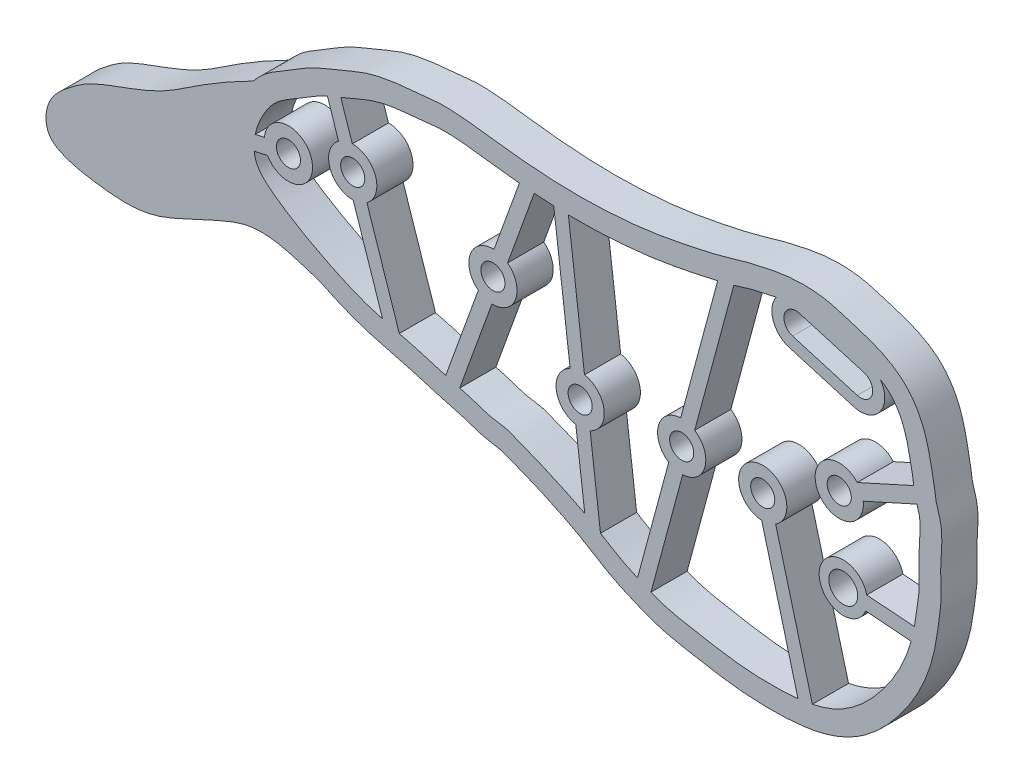
SolidWorks part; units mm, degrees
ref_plane "Спереди" through (0, 0, 0) normal (0, 0, 1) x (1, 0, 0)
ref_plane "Сверху" through (0, 0, 0) normal (0, 1, 0) x (1, 0, 0)
ref_plane "Справа" through (0, 0, 0) normal (1, 0, 0) x (0, 0, -1)
other "Configuration Table"
sketch "Sketch1" plane through (0, 0, 0) normal (0, 0, 1) x (1, 0, 0)
  line L0 (-54.4942, -36.8161) -> (-49.7734, -50.9593) construction
  line L5 (-50.4662, -50.7786) -> (-52.9099, -43.4575)
  line L6 (-54.1176, -39.8395) -> (-55.0485, -37.0505)
  line L8 (-52.9793, -39.4595) -> (-53.9346, -36.5976)
  line L9 (-51.7717, -43.0776) -> (-49.0827, -51.1337)
  line L10 (-44.6539, -52.3842) -> (-38.5095, -35.4122) construction
  line L11 (-6.4818, -51.4155) -> (-12.265, -50.9822) construction
  line L12 (-41.2312, -41.1674) -> (-39.127, -35.3552)
  line L14 (-37.8898, -35.4629) -> (-40.1029, -41.5759)
  line L15 (-42.5296, -44.7539) -> (-45.2324, -52.2194)
  line L16 (-41.4013, -45.1624) -> (-44.0733, -52.5428)
  line L17 (-33.0514, -56.7428) -> (-35.6666, -35.5833) construction
  line L18 (-36.274, -35.5605) -> (-34.9137, -46.5669)
  line L19 (-35.0602, -35.5983) -> (-33.7227, -46.4197)
  line L20 (-28.7671, -59.0348) -> (-22.0114, -33.9745) construction
  line L21 (-22.6779, -34.1417) -> (-25.7467, -45.5255)
  line L22 (-21.3407, -33.7919) -> (-24.5881, -45.8379)
  line L23 (-15.4183, -60.7418) -> (-18.9436, -47.5231) construction
  line L24 (-16.018, -60.8216) -> (-19.0319, -49.5205)
  line L25 (-14.8259, -60.6345) -> (-17.8724, -49.2112)
  line L26 (-6.3189, -41.3366) -> (-12.597, -44.1796) construction
  line L27 (-6.4229, -40.7251) -> (-11.1072, -42.8463)
  line L28 (-6.1531, -41.9202) -> (-10.6122, -43.9394)
  line L29 (-16.1872, -34.0479) -> (-10.8235, -35.627) construction
  line L34 (-34.1152, -53.0271) -> (-34.4458, -50.3524) construction
  line L35 (-34.4458, -50.3524) -> (-33.7016, -56.3739)
  line L37 (-33.2549, -50.2052) -> (-32.3983, -57.1358)
  line L43 (-26.7395, -49.2084) -> (-29.3266, -58.8049)
  line L45 (-25.5809, -49.5207) -> (-28.2081, -59.266)
  line L52 (-15.9048, -33.0886) -> (-10.541, -34.6677)
  line L55 (-42.5296, -44.7539) -> (-45.2324, -52.2194) construction
  line L56 (-6.36, -50.823) -> (-10.3184, -50.5264)
  line L57 (-6.36, -50.823) -> (-10.3184, -50.5264)
  line L58 (-16.4697, -35.0072) -> (-11.1059, -36.5863)
  line L59 (-16.1872, -34.0479) -> (-10.8235, -35.627) construction
  line L60 (-15.6224, -32.1293) -> (-10.2586, -33.7084)
  line L61 (-16.7521, -35.9665) -> (-11.3883, -37.5456)
  line L62 (-6.6306, -52.0061) -> (-10.408, -51.723)
  line L63 (-61.1201, -43.4425) -> (-58.2756, -42.8039) construction
  line L64 (-60.2679, -42.6363) -> (-61.0321, -42.8078)
  line L65 (-60.005, -43.8071) -> (-61.1153, -44.0564)
  arc A2 (-51.7717, -43.0776) -> (-52.9793, -39.4595) centre (-52.9446, -41.4585) ccw
  circle A3 centre (-52.9446, -41.4585) radius 1
  arc A4 (-41.4013, -45.1624) -> (-40.1029, -41.5759) centre (-41.3162, -43.1649) ccw
  circle A5 centre (-41.3162, -43.1649) radius 1
  arc A6 (-33.2549, -50.2052) -> (-33.7227, -46.4197) centre (-34.0843, -48.386) ccw
  circle A7 centre (-34.0843, -48.386) radius 1
  arc A8 (-25.5809, -49.5207) -> (-24.5881, -45.8379) centre (-25.6638, -47.5231) ccw
  circle A9 centre (-25.6638, -47.5231) radius 1
  circle A11 centre (-18.9436, -47.5231) radius 1
  arc A14 (-11.1072, -42.8463) -> (-10.6122, -43.9394) centre (-12.597, -44.1796) ccw
  circle A15 centre (-12.597, -44.1796) radius 1
  arc A20 (-17.8724, -49.2112) -> (-19.0319, -49.5205) centre (-18.9436, -47.5231) ccw
  arc A26 (-10.3184, -50.5264) -> (-10.408, -51.723) centre (-12.265, -50.9822) ccw
  circle A29 centre (-12.265, -50.9822) radius 1.2
  arc A30 (-15.9048, -33.0886) -> (-16.4697, -35.0072) centre (-16.1872, -34.0479) ccw
  arc A31 (-11.1059, -36.5863) -> (-10.541, -34.6677) centre (-10.8235, -35.627) ccw
  arc A32 (-54.1176, -39.8395) -> (-52.9099, -43.4575) centre (-52.9446, -41.4585) ccw
  arc A33 (-15.6224, -32.1293) -> (-16.7521, -35.9665) centre (-16.1872, -34.0479) ccw
  arc A34 (-11.3883, -37.5456) -> (-10.2586, -33.7084) centre (-10.8235, -35.627) ccw
  arc A37 (-41.2312, -41.1674) -> (-42.5296, -44.7539) centre (-41.3162, -43.1649) ccw
  arc A42 (-34.9137, -46.5669) -> (-34.4458, -50.3524) centre (-34.0843, -48.386) ccw
  arc A47 (-25.7467, -45.5255) -> (-26.7395, -49.2084) centre (-25.6638, -47.5231) ccw
  arc A49 (-56.5864, -44.0651) -> (-56.5834, -44.0611) centre (-58.2756, -42.8039) ccw
  arc A50 (-60.005, -43.8071) -> (-60.2679, -42.6363) centre (-58.2756, -42.8039) ccw
  circle A51 centre (-58.2756, -42.8039) radius 1
  spline S1 degree 3 poles (-58.7581, -48.9922) (-59.7104, -48.3888) (-60.601, -47.7689) (-61.439, -47.0975) (-62.1184, -46.3263) (-62.5768, -45.5944) (-62.8752, -44.6749) (-62.9472, -43.8512) (-62.9111, -43.1163) (-62.7679, -42.2009) (-62.4279, -41.1226) (-61.9297, -40.1381) (-61.4448, -39.3703) (-60.8782, -38.6441) (-60.0099, -37.8528) (-59.0035, -37.2461) (-58.1744, -36.7728) (-57.3271, -36.2387) (-56.3554, -35.6614) (-55.2169, -35.1525) (-54.2864, -34.812) (-53.4311, -34.4398) (-52.4291, -34.0078) (-51.2557, -33.61) (-50.0717, -33.3845) (-49.0452, -33.2306) (-47.8281, -33.1472) (-47.1214, -33.0685) (-45.8394, -32.9) (-44.6534, -32.9307) (-43.5686, -33.0146) (-42.1571, -33.1777) (-40.5095, -33.4038) (-38.5454, -33.6125) (-35.9409, -33.8049) (-33.3406, -33.8329) (-30.7567, -33.6781) (-28.7942, -33.4888) (-26.9201, -33.1962) (-24.9503, -32.8067) (-23.3497, -32.461) (-22.2655, -32.183) (-21.6495, -32.0089) (-21.2094, -31.8775) (-20.7095, -31.7135) (-19.878, -31.4995) (-19.1412, -31.3406) (-18.0288, -31.0843) (-16.5225, -30.8594) (-14.9286, -30.8163) (-13.4817, -31.0389) (-12.6301, -31.275) (-12.133, -31.4395) (-11.6411, -31.5873) (-10.8921, -31.8106) (-9.8671, -32.1394) (-8.5679, -32.7011) (-7.2519, -33.5877) (-6.2079, -34.8676) (-5.5594, -36.216) (-5.2408, -37.3079) (-5.0596, -38.1183) (-4.9425, -38.7029) (-4.8586, -39.1344) (-4.7764, -39.5181) (-4.6916, -40.024) (-4.6394, -40.5082) (-4.5811, -40.8969) (-4.4823, -41.2423) (-4.2813, -41.8514) (-4.1203, -42.6037) (-4.0747, -43.397) (-4.1171, -44.3126) (-4.1787, -45.2836) (-4.1993, -45.9221) (-4.1608, -46.9219) (-4.1506, -47.8891) (-4.2242, -48.6749) (-4.293, -49.0981) (-4.341, -49.3937) (-4.4, -49.8627) (-4.483, -50.5252) (-4.5958, -51.2074) (-4.7781, -52.079) (-5.1851, -53.5482) (-6.0146, -55.4786) (-7.3401, -57.5438) (-8.9971, -59.5041) (-11.088, -61.2325) (-13.7073, -62.3368) (-16.2947, -62.7054) (-18.6823, -62.767) (-21.1287, -62.6183) (-23.0787, -62.3194) (-24.5778, -62.0499) (-25.6889, -61.8523) (-26.8868, -61.6099) (-27.9556, -61.3023) (-28.7638, -60.9861) (-29.2891, -60.7653) (-29.7912, -60.5614) (-30.3561, -60.3273) (-30.9518, -60.0497) (-31.6951, -59.6598) (-32.5624, -59.1498) (-33.5293, -58.5502) (-34.7253, -57.8417) (-36.2969, -57.0762) (-38.0088, -56.3126) (-39.3047, -55.814) (-40.3059, -55.3901) (-40.6535, -55.2776) (-41.0437, -55.2098) (-41.6818, -55.1266) (-42.474, -54.929) (-43.0705, -54.7168) (-43.5262, -54.5599) (-43.9971, -54.425) (-44.7148, -54.2363) (-45.6675, -53.9705) (-47.1182, -53.541) (-48.8494, -53.0287) (-51.0345, -52.5269) (-53.2229, -51.8118) (-54.8479, -51.08) (-56.3053, -50.3685) (-57.5646, -49.6942) (-58.7581, -48.9922) (-59.7104, -48.3888) (-60.601, -47.7689) knots -0.027589 -0.015625 -0.007812 0 0.007812 0.015625 0.019531 0.023437 0.027344 0.03125 0.035156 0.039062 0.046875 0.054687 0.059556 0.063462 0.070312 0.078125 0.085937 0.09375 0.101562 0.109375 0.117187 0.125 0.132812 0.140625 0.148437 0.15625 0.164062 0.171875 0.179687 0.1875 0.195312 0.203125 0.21875 0.234375 0.25 0.28125 0.296875 0.3125 0.328125 0.34375 0.359375 0.367187 0.371094 0.375 0.378906 0.382812 0.390625 0.398437 0.40625 0.421875 0.429687 0.433594 0.4375 0.441406 0.445312 0.453125 0.460937 0.46875 0.476562 0.484375 0.492187 0.496094 0.5 0.503906 0.505859 0.507812 0.511719 0.515625 0.519531 0.523437 0.527344 0.53125 0.535156 0.539062 0.546875 0.554687 0.5625 0.566406 0.568359 0.570312 0.574219 0.578125 0.582031 0.585937 0.59375 0.609375 0.625 0.640625 0.65625 0.671875 0.6875 0.703125 0.71875 0.734375 0.742187 0.75 0.757812 0.765625 0.769531 0.773437 0.777344 0.78125 0.785156 0.789062 0.796875 0.804687 0.8125 0.828125 0.84375 0.851562 0.859375 0.863281 0.867187 0.871094 0.875 0.878906 0.882812 0.886719 0.890625 0.898437 0.90625 0.921875 0.9375 0.953125 0.964598 0.972411 0.984375 0.992187 1 1.007812 1.015625 1.019531 only from (-59.7001, -48.386) to (-59.7001, -48.386)
  spline S2 degree 3 poles (-54.8378, -49.1612) (-57.6604, -47.6241) (-59.8772, -46.0799) (-61.1016, -44.9748) (-61.19, -42.8792) (-60.5369, -41.1939) (-59.2773, -39.4251) (-57.3309, -38.4175) (-55.4721, -37.1478) (-53.2151, -36.3584) (-51.2833, -35.3978) (-49.5351, -35.1222) (-48.3072, -34.966) (-47.2995, -34.9312) (-45.9793, -34.697) (-43.9653, -34.742) (-40.8542, -35.194) (-36.962, -35.5881) (-33.9262, -35.6271) (-31.9892, -35.554) (-30.8887, -35.4887) (-29.5808, -35.3714) (-27.6433, -35.1578) (-24.6742, -34.6016) (-21.912, -33.9992) (-19.9812, -33.3713) (-19.0765, -33.1767) (-17.7192, -32.8438) (-15.8054, -32.5785) (-14.0131, -32.7113) (-11.5739, -33.5264) (-8.8287, -34.1518) (-7.065, -36.9423) (-6.7879, -38.7114) (-6.4527, -40.2945) (-6.4104, -41.2062) (-5.9587, -42.4484) (-5.8567, -43.2131) (-5.9542, -44.844) (-6.0378, -46.2993) (-5.8798, -47.7388) (-6.1409, -49.2063) (-6.4685, -52.3712) (-8.2087, -56.1917) (-12.2182, -60.2134) (-15.6942, -60.8453) (-17.4574, -60.9255) (-18.4504, -60.9397) (-19.983, -60.9127) (-22.1617, -60.661) (-24.8025, -60.1784) (-26.9948, -59.7888) (-28.675, -59.0656) (-30.7159, -58.261) (-33.245, -56.49) (-36.0164, -55.2271) (-37.9357, -54.4025) (-39.0582, -53.9787) (-40.2188, -53.4584) (-41.5664, -53.3759) (-42.8626, -52.8536) (-45.1527, -52.2761) (-48.0976, -51.3224) (-51.3756, -50.6084) (-54.8378, -49.1612) (-57.6604, -47.6241) (-59.8772, -46.0799) knots -0.078621 -0.053539 -0.039111 0 0.008418 0.024992 0.034759 0.054839 0.065896 0.084166 0.104395 0.11788 0.139207 0.153886 0.158466 0.167836 0.177148 0.189373 0.214163 0.249835 0.279723 0.284249 0.294647 0.305206 0.314606 0.339694 0.375025 0.37997 0.386562 0.396484 0.411656 0.431742 0.437535 0.469592 0.482501 0.504001 0.506417 0.516135 0.523104 0.532522 0.536639 0.545133 0.566484 0.569737 0.578233 0.624864 0.662471 0.68872 0.696194 0.699273 0.709375 0.72807 0.744781 0.765339 0.774026 0.78277 0.810922 0.837688 0.846033 0.85436 0.862697 0.872259 0.882004 0.891572 0.921379 0.946461 0.960889 1 1.008418 1.024992 1.034759 only from (-58.7055, -46.8858) to (-58.7055, -46.8858)
  spline S3 degree 3 poles (-61.1941, -39.0539) (-62.626, -39.7821) (-65.2082, -41.2079) (-68.8393, -43.8366) (-72.316, -44.9962) (-74.9893, -46.0569) (-76.7811, -47.3826) (-78.4745, -48.9002) (-78.4678, -51.4704) (-76.4876, -52.5204) (-73.8899, -52.9864) (-69.8015, -53.368) (-66.6063, -51.6264) (-63.7164, -50.3565) (-60.4815, -48.928) (-57.3243, -50.15) (-55.5648, -50.7285) knots 0 0 0 0 0.105046 0.193261 0.291014 0.343614 0.380043 0.43698 0.487582 0.515276 0.574689 0.662804 0.775463 0.804075 0.870738 1 1 1 1
  point P15 (-13.5054, -34.8374)
  point P22 (-13.5054, -34.8374)
  point P47 (-54.612, -36.8211)
  point P49 (-49.7734, -50.9822)
  point P51 (0, 0)
  point P55 (-42.4093, -52.975)
  point P61 (-19.7924, -49.2084)
  point P71 (0, 0)
  point P75 (-33.8709, -44.3599)
  point P87 (-44.6503, -52.3852)
  point P91 (-38.5095, -35.3552)
  point P106 (-34.1152, -48.386)
  point P113 (-19.0319, -47.5231)
  dimension "D19" = 2
  dimension "D6" = 0.6
  dimension "D10" = 0.6
  dimension "D14" = 0.6
  dimension "D15" = 0.6
  dimension "D11" = 0.6
  dimension "D12" = 0.6
  dimension "D4" = 0.6
  dimension "D5" = 0.6
  dimension "D8" = 0.6
  dimension "D3" = 0.6
  dimension "D9" = 0.6
  dimension "D16" = 0.6
  dimension "D13" = 1
  dimension "D17" = 0.6
  dimension "D18" = 0.6
  dimension "D2" = 0.6
  dimension "D7" = 0.6
extrude "Boss-Extrude2" add sketch "Sketch1" along normal blind 3 contours S1 S2 A33 L60 A34 | S2 L65 A50 L64 | A50 A51 | S2 L6 A32 L5 L9 A2 L8 A3 | S2 L12 A37 L15 L16 A4 L14 A5 | S2 L18 A42 L35 L37 A6 L19 A7 | S2 L21 A47 L43 L45 A8 L22 A9 | S2 L25 A20 L24 A11 | S2 L56 A26 L62 A29 | S2 L27 A14 L28 A15 | S2 A33 L61 A34 A31 L58 A30 L52 | A33 S2 A34 L60 | S1 S3 region at (-52.2974, -43.3835, 0) region at (-43.7053, -48.5503, 0) region at (-61.0565, -43.4339, 0) region at (-34.3133, -46.5096, 0) region at (-27.7753, -54.0761, 0) region at (-17.7361, -52.0481, 0) region at (-10.8571, -51.0859, 0) region at (-13.4094, -33.0375, 0) region at (-16.8137, -32.2432, 0) region at (-11.0372, -43.4711, 0) region at (-68.8436, -47.8458, 0) region at (-62.2466, -44.1119, 0)
equation "\"R small\"= 2"
equation "\"R big\"= 4"
equation "\"width\"= 0.6"
equation "\"D5@Sketch1\"=\"width\""
equation "\"D4@Sketch1\"=\"width\""
equation "\"D3@Sketch1\"=\"width\""
equation "\"D9@Sketch1\"=\"width\""
equation "\"D8@Sketch1\"=\"width\""
equation "\"D6@Sketch1\"=\"width\""
equation "\"D10@Sketch1\"=\"width\""
equation "\"D16@Sketch1\"=\"width\""
equation "\"D11@Sketch1\"=\"width\""
equation "\"D12@Sketch1\"=\"width\""
equation "\"D14@Sketch1\"=\"width\""
equation "\"D15@Sketch1\"=\"width\""
equation "\"border width\"= 1"
equation "\"D13@Sketch1\"=\"border width\""
equation "\"D17@Sketch1\"=\"width\""
equation "\"D18@Sketch1\"=\"width\""
equation "\"depth\"= 3"
equation "\"D2@Sketch1\"=\"width\""
equation "\"D7@Sketch1\"=\"width\""
equation "\"D19@Sketch1\"=\"R small\""
